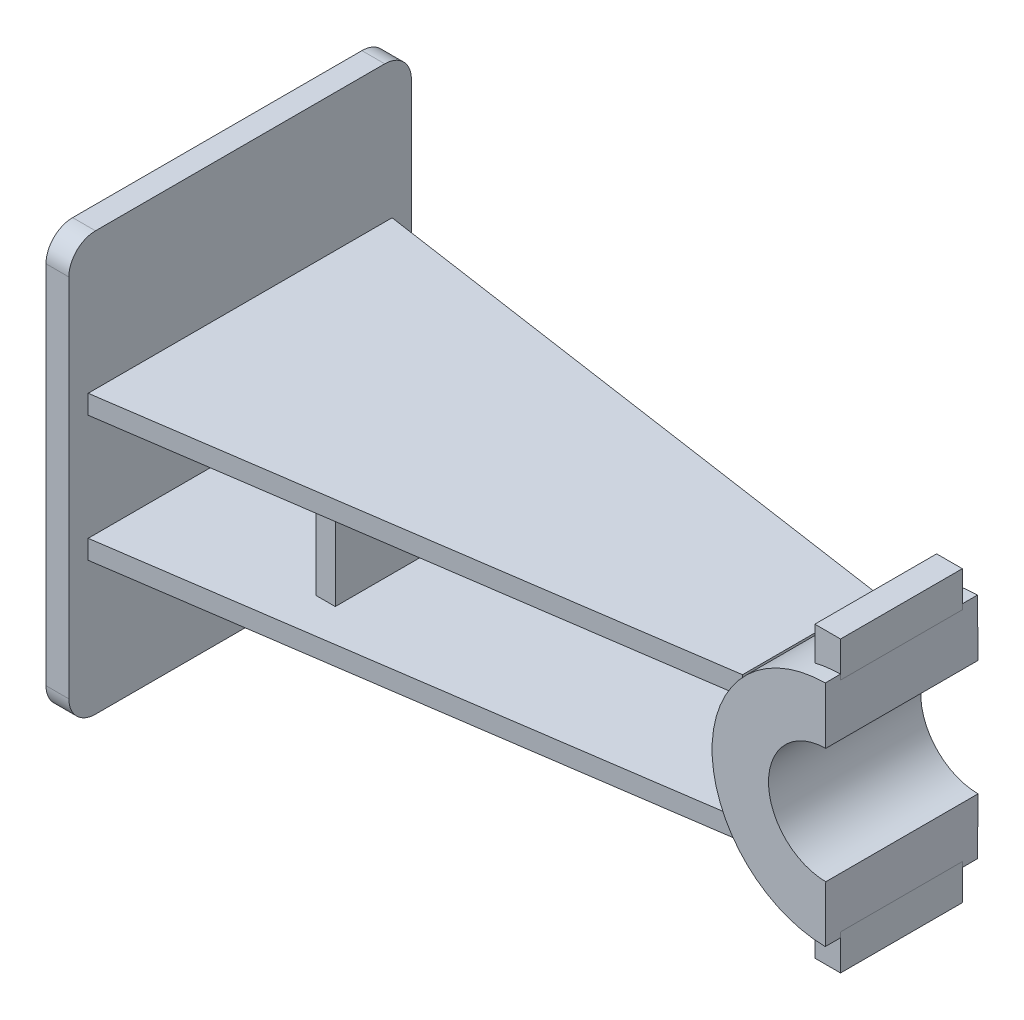
SolidWorks part; units mm, degrees
material "AISI Type 316L stainless steel"
ref_plane "Front Plane" through (0, 0, 0) normal (0, 0, 1) x (1, 0, 0)
ref_plane "Top Plane" through (0, 0, 0) normal (0, 1, 0) x (1, 0, 0)
ref_plane "Right Plane" through (0, 0, 0) normal (1, 0, 0) x (0, 0, -1)
sketch "Extrude sketch 1" plane through (0, 0, 0) normal (1, 0, 0) x (0, 0, -1)
  line L0 (-90, 96) -> (-90, -96)
  line L1 (-76, -110) -> (76, -110)
  line L2 (90, -96) -> (90, 96)
  line L3 (76, 110) -> (-76, 110)
  arc A0 (-90, -96) -> (-76, -110) centre (-76, -96) ccw
  arc A1 (76, -110) -> (90, -96) centre (76, -96) ccw
  arc A2 (90, 96) -> (76, 110) centre (76, 96) ccw
  arc A3 (-76, 110) -> (-90, 96) centre (-76, 96) ccw
  dimension "D1" = 14
  dimension "D2" = 180
  dimension "D3" = 220
extrude "Extrude 1" add sketch "Extrude sketch 1" along normal blind 12 from offset 360 separate body offset against normal yes
sketch "Extrude sketch 2" plane through (0, 0, 0) normal (0, 1, 0) x (1, 0, 0)
  line L0 (-349, 80) -> (-48, 36)
  line L1 (-48, 36) -> (-48, -36)
  line L2 (-48, -36) -> (-349, -80)
  line L3 (-349, -80) -> (-349, 80)
  dimension "D1" = 301
  dimension "D2" = 44
  dimension "D3" = 116
extrude "Extrude 2" add sketch "Extrude sketch 2" along normal blind 10 from offset 28 separate body
sketch "Extrude sketch 3" plane through (0, 0, 0) normal (0, 1, 0) x (1, 0, 0)
  line L0 (-349, 80) -> (-48, 36)
  line L1 (-48, 36) -> (-48, -36)
  line L2 (-48, -36) -> (-349, -80)
  line L3 (-349, -80) -> (-349, 80)
  dimension "D1" = 301
  dimension "D2" = 44
  dimension "D3" = 116
extrude "Extrude 3" add sketch "Extrude sketch 3" along normal blind 10 from offset 38 separate body offset against normal yes
sketch "Extrude sketch 4" plane through (0, 0, 0) normal (0, 0, 1) x (1, 0, 0)
  line L0 (-252, -28) -> (-252, 28)
  line L1 (-252, 28) -> (-262, 28)
  line L2 (-262, 28) -> (-262, -28)
  line L3 (-262, -28) -> (-252, -28)
  dimension "D1" = 10
  dimension "D2" = 56
extrude "Extrude 4" add sketch "Extrude sketch 4" along normal blind 92 from offset 46 separate body offset against normal yes
sketch "Revolve profile 1" plane through (0, 0, 0) normal (0, 1, 0) x (1, 0, 0)
  line L0 (60, 40) -> (60, -40)
  line L1 (60, -40) -> (30.35, -40)
  line L2 (30.35, -40) -> (30.35, 40)
  line L3 (30.35, 40) -> (60, 40)
  line L4 (0, 45) -> (0, -45) construction
  dimension "D1" = 29.65
  dimension "D2" = 60
  dimension "D3" = 80
revolve "Revolve 1" add sketch "Revolve profile 1" angle 179 about L4
move or copy body "Revolve index 1" bodies to move or copy 105 copy no rotation origin (0, 0, 0) rotation axis (0, 0, 1) rotation angle 90.5
sketch "Extrude sketch 5" plane through (0, 0, 0) normal (0, 0, 1) x (1, 0, 0)
  line L0 (-0.5, 56) -> (-0.5, 76)
  line L1 (-0.5, 76) -> (-14, 76)
  line L2 (-14, 76) -> (-14, 56)
  line L3 (-14, 56) -> (-0.5, 56)
  dimension "D1" = 13.5
  dimension "D2" = 20
extrude "Extrude 5" add sketch "Extrude sketch 5" along normal blind 64 from offset 32 separate body offset against normal yes
sketch "Extrude sketch 6" plane through (0, 0, 0) normal (0, 0, 1) x (1, 0, 0)
  line L0 (-0.5, -76) -> (-0.5, -56)
  line L1 (-0.5, -56) -> (-14, -56)
  line L2 (-14, -56) -> (-14, -76)
  line L3 (-14, -76) -> (-0.5, -76)
  dimension "D1" = 13.5
  dimension "D2" = 20
extrude "Extrude 6" add sketch "Extrude sketch 6" along normal blind 64 from offset 32 separate body offset against normal yes
combine bodies "Combine (weld / assembly of features)" operation type add bodies to combine 108 102 106 103 104 107 101
